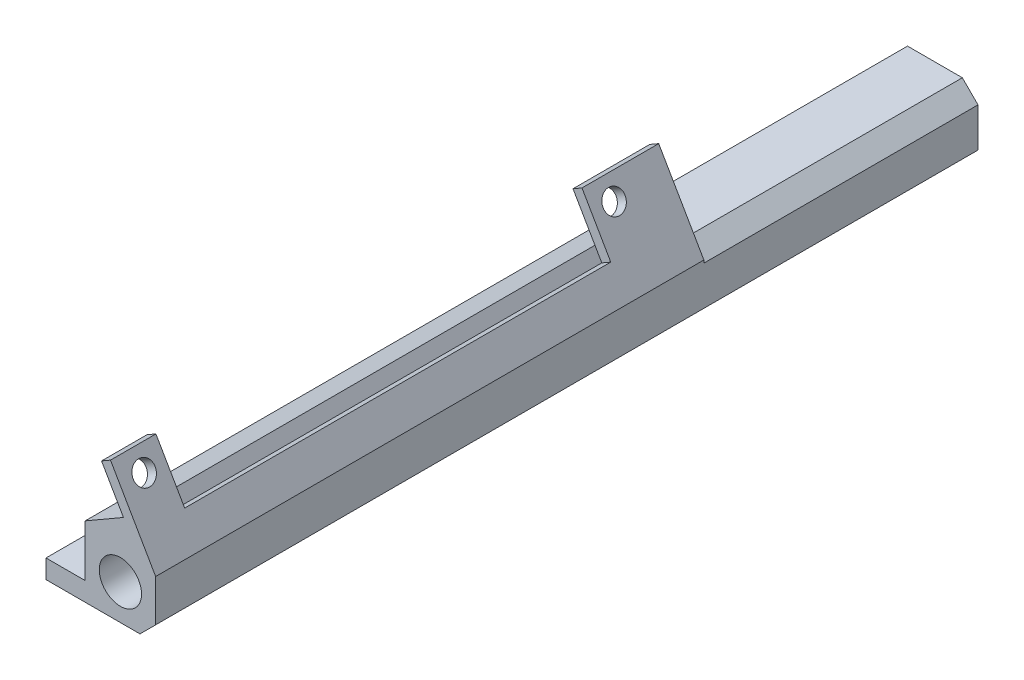
SolidWorks part; units mm, degrees
other "Markup1"
sketch "Sketch18" plane through (59.69, 0, 0) normal (0, 0, 1) x (1, 0, 0)
sketch "Sketch20" plane through (59.69, 0, 0) normal (0, 0, 1) x (1, 0, 0)
other "Markup2"
sketch "Sketch19" plane through (59.69, 0, 0) normal (0, 0, 1) x (1, 0, 0)
sketch "Sketch21" plane through (59.69, 0, 0) normal (0, 0, 1) x (1, 0, 0)
ref_plane "Front Plane" through (0, 0, 0) normal (0, 0, 1) x (1, 0, 0)
ref_plane "Top Plane" through (0, 0, 0) normal (0, 1, 0) x (1, 0, 0)
ref_plane "Right Plane" through (0, 0, 0) normal (1, 0, 0) x (0, 0, -1)
sketch "Sketch1" plane through (0, 0, 0) normal (0, 1, 0) x (1, 0, 0)
  line L1 (0, 0) -> (77.47, 0)
  line L2 (0, 0) -> (0, 133.35)
  line L3 (0, 133.35) -> (77.47, 133.35)
  line L4 (77.47, 0) -> (77.47, 133.35)
  dimension "D1" = 77.47
  dimension "D2" = 133.35
extrude "Boss-Extrude1" add sketch "Sketch1" along normal blind 11.43
sketch "Sketch2" plane through (0, 0, 0) normal (0, 0, 1) x (1, 0, 0)
  line L0 (5.715, 5.715) -> (71.755, 5.715) construction
  line L1 (38.735, 11.43) -> (38.735, 0) construction
  line L2 (0, 11.43) -> (77.47, 11.43) construction
  line L3 (0, 0) -> (77.47, 0) construction
  circle A0 centre (5.715, 5.715) radius 3.429
  circle A1 centre (71.755, 5.715) radius 3.429
  point P10 (38.735, 5.715)
  dimension "D1" = 6.858
  dimension "D2" = 66.04
extrude "Cut-Extrude1" cut sketch "Sketch2" against normal through all
sketch "Sketch3" plane through (0, 11.43, 0) normal (0, 1, 0) x (1, 0, 0)
  line L0 (11.43, 133.35) -> (11.43, 95.25)
  line L1 (77.47, 133.35) -> (0, 133.35) construction
  line L2 (11.43, 133.35) -> (66.04, 133.35)
  line L3 (66.04, 133.35) -> (66.04, 95.25)
  line L4 (53.34, 82.55) -> (24.13, 82.55)
  line L5 (0, 133.35) -> (0, 0) construction
  arc A0 (66.04, 95.25) -> (53.34, 82.55) centre (53.34, 95.25) cw
  arc A1 (24.13, 82.55) -> (11.43, 95.25) centre (24.13, 95.25) cw
  point P10 (38.735, 133.35)
  dimension "D1" = 12.7
  dimension "D2" = 11.43
  dimension "D3" = 50.8
extrude "Cut-Extrude2" cut sketch "Sketch3" against normal through all
sketch "Sketch4" plane through (0, 0, -133.35) normal (0, 0, -1) x (-1, 0, 0)
  line L0 (-11.43, 0) -> (-11.43, 11.43) construction
  line L1 (-66.04, 11.43) -> (-11.43, 11.43)
  line L2 (-66.04, 11.43) -> (-66.04, 5.08)
  line L3 (-66.04, 5.08) -> (-11.43, 5.08)
  line L4 (-11.43, 11.43) -> (-11.43, 5.08)
  line L5 (-11.43, 0) -> (0, 0) construction
  dimension "D1" = 5.08
extrude "Cut-Extrude3" cut sketch "Sketch4" against normal through all
chamfer "Chamfer1" distance 2.54 angle 45 4 edges at (0, 0, -66.675) (0, 11.43, -66.675) (77.47, 0, -66.675) (77.47, 11.43, -66.675)
sketch "Sketch5" plane through (0, 11.43, 0) normal (0, 1, 0) x (1, 0, 0)
  line L0 (66.04, 82.55) -> (0, 82.55)
  line L1 (66.04, 0) -> (66.04, 95.25) construction
  line L2 (0, 0) -> (0, 133.35) construction
  line L3 (0, 82.55) -> (0, 133.35)
  line L4 (0, 133.35) -> (66.04, 133.35)
  line L5 (66.04, 133.35) -> (66.04, 82.55)
  line L6 (24.13, 82.55) -> (53.34, 82.55) construction
extrude "Cut-Extrude4" cut sketch "Sketch5" against normal through all
sketch "Sketch6" plane through (0, 11.43, 0) normal (0, 1, 0) x (1, 0, 0)
  line L0 (53.34, 82.55) -> (53.34, 0)
  line L1 (11.43, 82.55) -> (66.04, 82.55) construction
  line L2 (66.04, 0) -> (11.43, 0) construction
  line L3 (53.34, 0) -> (0, 0)
  line L4 (0, 0) -> (0, 82.55)
  line L5 (0, 82.55) -> (53.34, 82.55)
  line L6 (66.04, 0) -> (66.04, 133.35) construction
  dimension "D1" = 12.7
extrude "Cut-Extrude5" cut sketch "Sketch6" against normal through all
sketch "Sketch7" plane through (0, 5.08, 0) normal (0, 1, 0) x (1, 0, 0)
  line L0 (53.34, 82.55) -> (66.04, 82.55) construction
  line L1 (66.04, 0) -> (66.04, 82.55) construction
  circle A0 centre (62.23, 74.93) radius 1.778
  circle A4 centre (62.23, 13.97) radius 1.778
  dimension "D1" = 3.556
  dimension "D2" = 7.62
  dimension "D3" = 68.58
  dimension "D4" = 3.81
extrude "Hole Cuts 1" cut sketch "Sketch7" against normal through all
sketch "Sketch8" plane through (0, 0, 0) normal (0, 0, 1) x (1, 0, 0)
  line L0 (77.47, 11.8699) -> (77.47, 8.89)
  line L1 (77.47, 11.8699) -> (71.882, 21.5486)
  line L2 (71.882, 21.5486) -> (68.6183, 19.6643)
  line L3 (68.6183, 19.6643) -> (71.5393, 14.605)
  line L4 (71.5393, 14.605) -> (66.04, 11.43)
  line L5 (77.47, 11.43) -> (68.58, 11.43) construction
  line L6 (66.04, 11.43) -> (74.93, 11.43) construction
  line L7 (66.04, 11.43) -> (74.93, 11.43)
  line L9 (77.47, 8.89) -> (77.47, 2.54) construction
  line L10 (74.93, 11.43) -> (77.47, 8.89)
  dimension "D2" = 11.176
  dimension "D3" = 6.35
  dimension "D4" = 5.842
  dimension "D6" = 60
extrude "Boss-Extrude2" add sketch "Sketch8" against normal blind 88.9
sketch "Sketch9" plane through (0, 0, 0) normal (0, 0, 1) x (1, 0, 0)
  line L0 (74.93, 0) -> (66.04, 0) construction
  line L1 (53.34, 0) -> (74.93, 0) construction
  line L3 (66.04, 0) -> (59.69, 0) construction
  line L4 (59.69, 0) -> (53.34, 0)
  line L5 (53.34, 0) -> (53.34, 5.08)
  line L6 (53.34, 5.08) -> (59.69, 5.08)
  line L7 (66.04, 5.08) -> (53.34, 5.08) construction
  line L8 (59.69, 5.08) -> (59.69, 0)
  dimension "D1" = 6.35
extrude "Cut-Extrude7" cut sketch "Sketch9" against normal up to next
sketch "Sketch10" plane through (0, 0, 0) normal (0, 0, 1) x (1, 0, 0)
  line L0 (59.69, 5.08) -> (66.04, 5.08)
  line L1 (66.04, 5.08) -> (66.04, 3.81)
  line L2 (66.04, 3.81) -> (59.69, 3.81)
  line L3 (59.69, 0) -> (59.69, 5.08) construction
  line L4 (59.69, 3.81) -> (59.69, 5.08)
  line L5 (59.69, 0) -> (74.93, 0) construction
  dimension "D1" = 3.81
extrude "Cut-Extrude8" cut sketch "Sketch10" against normal up to next
sketch "Sketch11" plane through (59.9786, 34.6287, 0) normal (-0.866, -0.5, 0) x (0, 0, 1)
  line L0 (-88.9, -23.1213) -> (0, -23.1213) construction
  line L2 (0, -17.2793) -> (0, -23.1213) construction
  circle A0 centre (-3.81, -19.3113) radius 1.778
  circle A1 centre (-80.01, -19.3113) radius 1.778
  dimension "D1" = 3.556
  dimension "D4" = 76.2
  dimension "D3" = 3.81
  dimension "D2" = 3.81
extrude "Hole Cuts 2" cut sketch "Sketch11" against normal up to next
sketch "Sketch12" plane through (63.2423, 36.513, 0) normal (0.866, 0.5, 0) x (0, 0, -1)
  line L1 (88.9, -17.2793) -> (0, -17.2793)
  line L2 (88.9, -17.2793) -> (88.9, -28.4553)
  line L3 (88.9, -28.4553) -> (0, -28.4553)
  line L4 (0, -17.2793) -> (0, -28.4553)
extrude "Cut-Extrude10" cut sketch "Sketch12" against normal blind 1.27
sketch "Sketch22" plane through (0, 0, 0) normal (0, 0, 1) x (1, 0, 0)
  line L0 (-928.245, 5.715) -> (49071.755, 5.715) construction
  line L1 (71.755, 5.715) -> (64.2465, 18.7201) construction
  line L2 (64.9306, 17.5352) -> (69.33, 20.0752)
  line L3 (64.9306, 17.5352) -> (67.8516, 12.4759)
  line L4 (69.33, 20.0752) -> (72.251, 15.0159)
  line L5 (67.8516, 12.4759) -> (72.251, 15.0159)
  line L6 (70.7821, 20.9136) -> (68.6183, 19.6643) construction
  line L7 (71.5393, 14.605) -> (66.04, 11.43) construction
  point P11 (0, 0)
  dimension "D1" = 60
  dimension "D2" = 5.08
extrude "Cut-Extrude15" cut sketch "Sketch22" against normal through all
sketch "Sketch14" plane through (0, 3.81, 0) normal (0, 1, 0) x (1, 0, 0)
  line L1 (59.69, 82.55) -> (66.04, 82.55)
  line L2 (59.69, 82.55) -> (59.69, 0)
  line L3 (59.69, 0) -> (66.04, 0)
  line L4 (66.04, 82.55) -> (66.04, 0)
extrude "Cut-Extrude12" cut sketch "Sketch14" against normal blind 0.762
sketch "Sketch15" plane through (8.6397, -14.9643, 0) normal (-0.5, 0.866, 0) x (0.866, 0.5, 0)
  line L1 (71.756, 0) -> (70.0792, 0)
  line L2 (71.756, 0) -> (71.756, 88.9)
  line L3 (71.756, 88.9) -> (70.0792, 88.9)
  line L4 (70.0792, 0) -> (70.0792, 88.9)
  point P6 (0, 0)
  point P7 (70.0792, 88.9)
extrude "Boss-Extrude3" add sketch "Sketch15" along normal blind 1.27
sketch "Sketch16" plane through (60.6903, 35.0396, 0) normal (-0.866, -0.5, 0) x (0, 0, 1)
  line L0 (-80.01, -19.3113) -> (-3.81, -19.3113) construction
  line L1 (-88.9, -16.0093) -> (0, -16.0093) construction
  line L2 (-76.454, -16.0093) -> (-7.366, -16.0093)
  line L3 (-76.454, -16.0093) -> (-76.454, -25.3438)
  line L4 (-76.454, -25.3438) -> (-7.366, -25.3438)
  line L5 (-7.366, -16.0093) -> (-7.366, -25.3438)
  point P12 (-41.91, -19.3113)
  point P13 (-41.91, -16.0093)
  dimension "D1" = 69.088
  dimension "D2" = 9.3345
extrude "Cut-Extrude13" cut sketch "Sketch16" against normal up to next
sketch "Sketch17" plane through (14.2277, -24.643, 0) normal (-0.5, 0.866, 0) x (0.866, 0.5, 0)
  line L1 (71.756, 88.9) -> (73.026, 88.9)
  line L2 (71.756, 88.9) -> (71.756, 0)
  line L3 (71.756, 0) -> (73.026, 0)
  line L4 (73.026, 88.9) -> (73.026, 0)
extrude "Cut-Extrude14" cut sketch "Sketch17" against normal up to next
